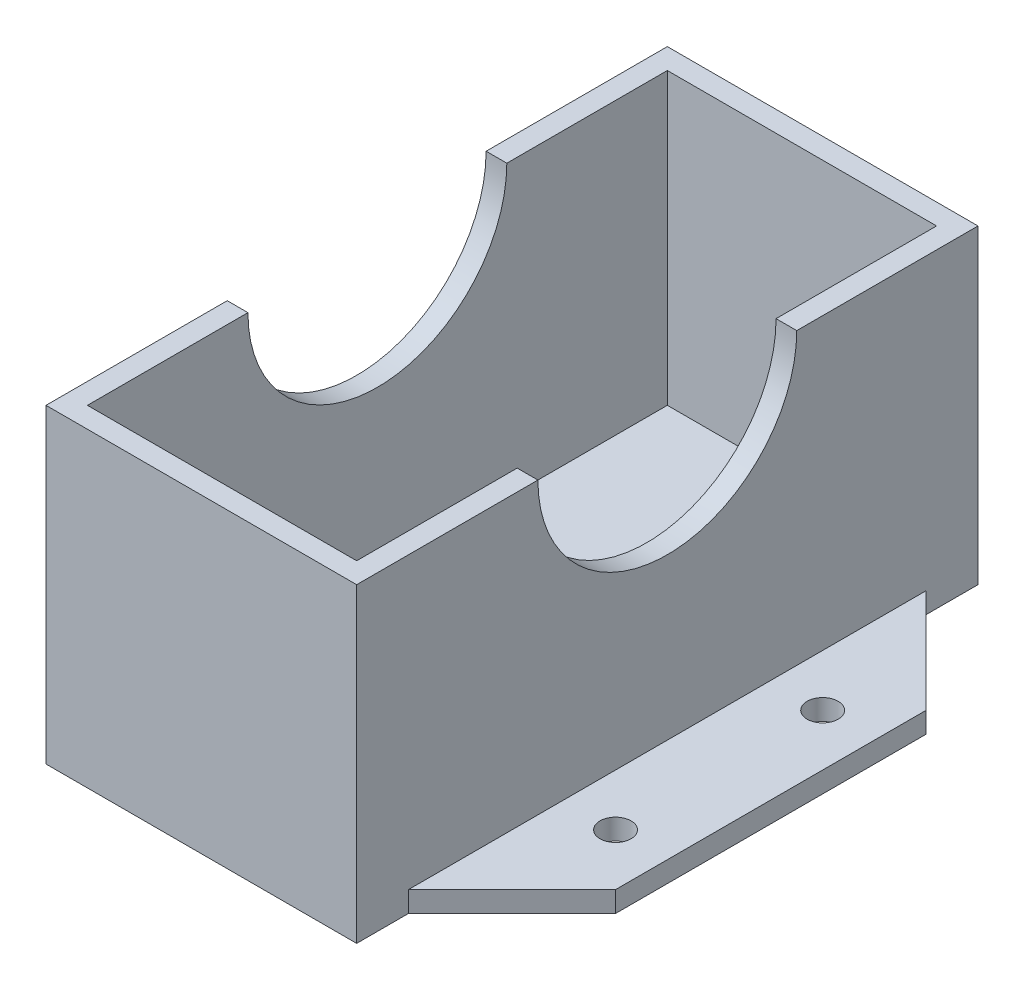
SolidWorks part; units mm, degrees
material "PLA 50%"
ref_plane "Front Plane" through (0, 0, 0) normal (0, 0, 1) x (1, 0, 0)
ref_plane "Top Plane" through (0, 0, 0) normal (0, 1, 0) x (1, 0, 0)
ref_plane "Right Plane" through (0, 0, 0) normal (1, 0, 0) x (0, 0, -1)
ref_axis "X" through (-88.99, 0, 0) along (1, 0, 0)
ref_axis "Y" through (0, 55, 0) along (0, -1, 0)
ref_axis "Z" through (0, 0, -88.99) along (0, 0, 1)
sketch "Sketch1" plane through (0, 0, 0) normal (0, 1, 0) x (1, 0, 0)
  line L0 (0, -30) -> (0, 30)
  line L5 (0, 30) -> (-15, 30)
  line L6 (-15, 30) -> (-15, 25)
  line L7 (-15, 25) -> (-25, 15)
  line L8 (-25, 15) -> (-25, -15)
  line L10 (-15, -25) -> (-15, -30)
  line L11 (-15, -30) -> (0, -30)
  line L12 (-15, -25) -> (-25, -15)
  line L17 (-20, -10) -> (-20, 10) construction
  line L18 (-15, 0) -> (-25, 0) construction
  circle A0 centre (-20, 10) radius 1.5
  circle A1 centre (-20, -10) radius 1.5
  point P3 (0, 0)
  point P13 (-25, 19.0446)
  point P14 (-15, -19.9583)
  point P15 (-25, -13.7929)
  point P16 (-15, 24.0683)
  point P17 (-20, 0)
  point P20 (-20, 0)
  point P21 (-15, 25.7224)
  dimension "D5" = 3
  dimension "D1" = 5
  dimension "D2" = 15
  dimension "D3" = 10
  dimension "D4" = 60
  dimension "D6" = 20
  dimension "D7" = 135
extrude "Boss-Extrude1" add sketch "Sketch1" along normal blind 2
mirror "Mirror1" about plane through (0, 0, 0) normal (1, 0, 0) of "Boss-Extrude1"
sketch "Sketch2" plane through (0, 2, 0) normal (0, 1, 0) x (1, 0, 0)
  line L0 (-13, 28) -> (-13, -28)
  line L1 (-15, 30) -> (15, 30)
  line L2 (-15, 30) -> (-15, -30)
  line L3 (-15, -30) -> (15, -30)
  line L4 (15, 30) -> (15, -30)
  line L5 (-13, -28) -> (13, -28)
  line L6 (13, 28) -> (13, -28)
  line L7 (-13, 28) -> (13, 28)
  dimension "D1" = 2
extrude "Boss-Extrude2" add sketch "Sketch2" along normal blind 28
sketch "Sketch3" plane through (15, 0, 0) normal (1, 0, 0) x (0, 0, -1)
  line L0 (-30, 30) -> (30, 30) construction
  circle A0 centre (0, 30) radius 12.5
  dimension "D1" = 25
extrude "Cut-Extrude1" cut sketch "Sketch3" against normal through all
